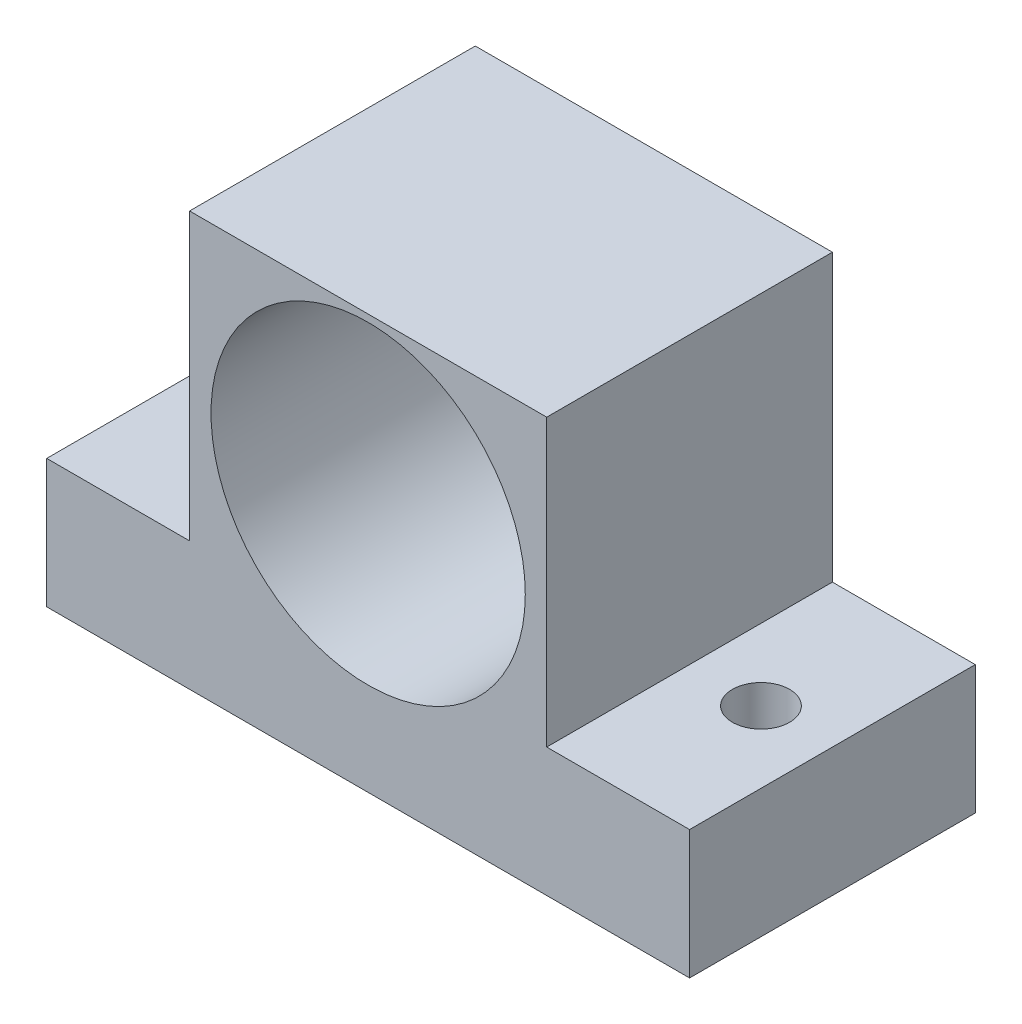
SolidWorks part; units mm, degrees
material "ABS"
ref_plane "Front Plane" through (0, 0, 0) normal (0, 0, 1) x (1, 0, 0)
ref_plane "Top Plane" through (0, 0, 0) normal (0, 1, 0) x (1, 0, 0)
ref_plane "Right Plane" through (0, 0, 0) normal (1, 0, 0) x (0, 0, -1)
sketch "Sketch1" plane through (0, 0, 0) normal (0, 0, 1) x (1, 0, 0)
  line L1 (-12.5, 11.5) -> (12.5, 11.5)
  line L2 (-12.5, 11.5) -> (-12.5, -17.5)
  line L3 (-12.5, -17.5) -> (12.5, -17.5)
  line L4 (12.5, 11.5) -> (12.5, -17.5)
  line L5 (-12.5, 11.5) -> (12.5, -17.5) construction
  line L6 (-12.5, -17.5) -> (12.5, 11.5) construction
  line L7 (12.5, -17.5) -> (22.5, -17.5)
  line L8 (12.5, -17.5) -> (12.5, -8.5)
  line L9 (12.5, -8.5) -> (22.5, -8.5)
  line L10 (22.5, -17.5) -> (22.5, -8.5)
  line L11 (12.5, -17.5) -> (22.5, -8.5) construction
  line L12 (12.5, -8.5) -> (22.5, -17.5) construction
  line L13 (-12.5, -17.5) -> (-22.5, -17.5)
  line L14 (-12.5, -17.5) -> (-12.5, -8.5)
  line L15 (-12.5, -8.5) -> (-22.5, -8.5)
  line L16 (-22.5, -17.5) -> (-22.5, -8.5)
  line L17 (-12.5, -17.5) -> (-22.5, -8.5) construction
  line L18 (-12.5, -8.5) -> (-22.5, -17.5) construction
  circle A0 centre (0, 0) radius 4.1
  circle A1 centre (0, 0) radius 11
  point P8 (0, 0)
  point P14 (17.5, -13)
  point P16 (-17.5, -13)
  dimension "D4" = 8.2
  dimension "D5" = 22
  dimension "D1" = 11.5
  dimension "D2" = 29
  dimension "D3" = 25
  dimension "D6" = 10
  dimension "D7" = 9
  dimension "D8" = 10
  dimension "D9" = 9
  dimension "D10" = 12.5
extrude "Boss-Extrude1" add sketch "Sketch1" along normal blind 20 contours L4 L1 L2 L3 A1 | L16 L13 L2 L15 | L7 L10 L9 L4 region at (0, 11.1171, 0) region at (-17.5, -13, 0) region at (17.5, -13, 0)
sketch "Sketch2" plane through (0, -8.5, 0) normal (0, 1, 0) x (1, 0, 0)
  line L0 (-22.5, 0) -> (-12.5, -20)
  line L1 (-12.5, -20) -> (-22.5, -20)
  line L2 (-22.5, -20) -> (-12.5, 0)
  line L3 (12.5, 0) -> (22.5, -20)
  line L4 (22.5, -20) -> (22.5, 0)
  line L5 (22.5, 0) -> (12.5, -20)
  circle A0 centre (-17.5, -10) radius 2
  circle A1 centre (17.5, -10) radius 2
  dimension "D1" = 4
  dimension "D2" = 4
extrude "Cut-Extrude1" cut sketch "Sketch2" against normal blind 9 contours L0 A0 L2 | L2 A0 L0 | L0 A0 L2 | L2 A0 L0 | A1 region at (-17.5, -8.5, 8.7139) region at (-18.5772, -8.5, 10) region at (-16.4228, -8.5, 10) region at (-17.5, -8.5, 11.2861)
